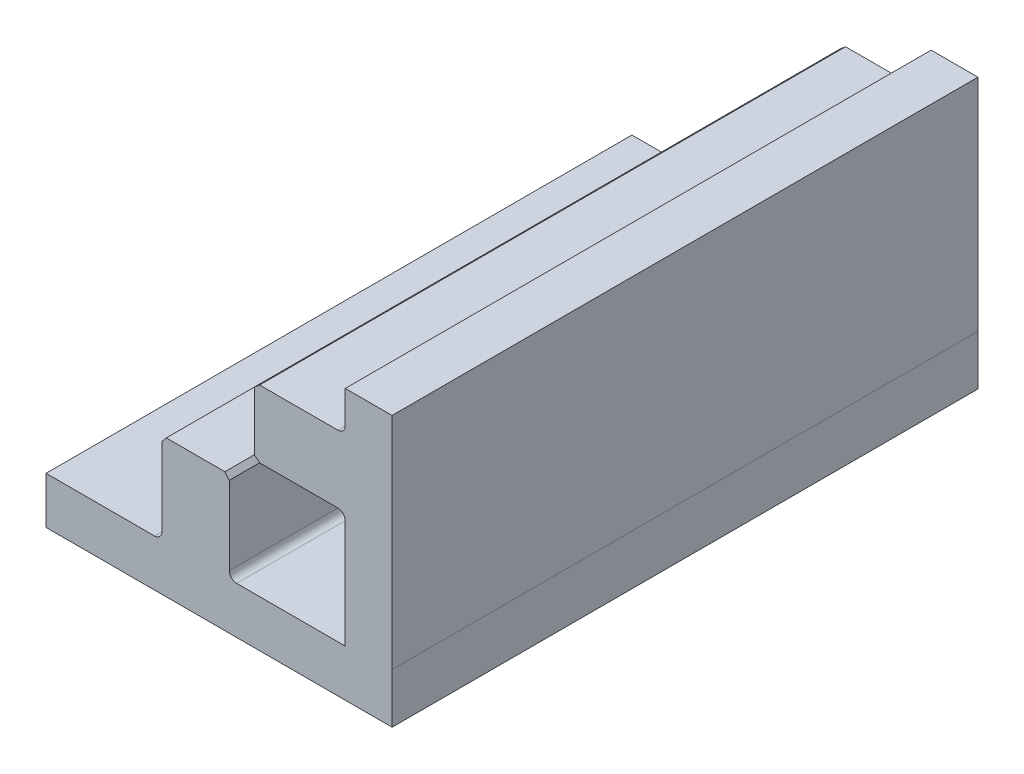
SolidWorks part; units mm, degrees
ref_plane "Front Plane" through (0, 0, 0) normal (0, 0, 1) x (1, 0, 0)
ref_plane "Top Plane" through (0, 0, 0) normal (0, 1, 0) x (1, 0, 0)
ref_plane "Right Plane" through (0, 0, 0) normal (1, 0, 0) x (0, 0, -1)
ref_plane "Plane1" through (0, 0, -3683) normal (0, 0, -1) x (-1, 0, 0)
sketch "Sketch1" plane through (0, 0, -3683) normal (0, 0, -1) x (-1, 0, 0)
  line L0 (7.9453, 3.5889) -> (-1.1987, 3.5889)
  line L1 (-1.8337, 4.2239) -> (-1.8337, 5.7479)
  line L2 (-1.1987, 6.3829) -> (1.6216, 6.3829)
  line L3 (1.6216, 6.3829) -> (1.6216, 6.8909)
  line L4 (1.6216, 6.8909) -> (-2.2147, 11.4629)
  line L5 (-2.2147, 11.4629) -> (-7.2947, 11.4629)
  line L6 (-7.2947, 11.4629) -> (-11.1311, 6.8909)
  line L7 (-11.1311, 6.8909) -> (-11.1311, 6.3829)
  line L8 (-11.1311, 6.3829) -> (-8.3107, 6.3829)
  line L9 (-7.6757, 5.7479) -> (-7.6757, 4.2239)
  line L10 (-8.3107, 3.5889) -> (-17.4547, 3.5889)
  line L11 (-17.7279, 3.8588) -> (-17.7284, 13.0024)
  line L12 (-17.4548, -0.4751) -> (7.9452, -0.4751)
  line L13 (-17.0929, 13.6378) -> (-15.5689, 13.6378)
  line L29 (-17.4547, 3.5889) -> (-17.7279, 3.5889)
  line L30 (-17.4548, -0.4751) -> (-17.7279, -0.4751)
  line L32 (8.2155, 3.5889) -> (8.2155, -0.4751)
  line L34 (8.2155, 3.5889) -> (7.9453, 3.5889)
  line L35 (8.2155, -0.4751) -> (7.9452, -0.4751)
  line L36 (-14.9339, 13.0028) -> (-14.9339, 10.1825)
  line L37 (-14.9339, 10.1825) -> (-14.4259, 10.1825)
  line L38 (-14.4259, 10.1825) -> (-9.8539, 14.0188)
  line L39 (-9.8539, 14.0188) -> (-9.8539, 19.0988)
  line L40 (-9.8539, 19.0988) -> (-14.4259, 22.9352)
  line L41 (-14.4259, 22.9352) -> (-14.9339, 22.9352)
  line L42 (-14.9339, 22.9352) -> (-14.9339, 20.1148)
  line L43 (-15.5689, 19.4798) -> (-17.0929, 19.4798)
  line L44 (-17.7287, 20.1156) -> (-17.7288, 22.9352)
  line L45 (-21.7872, 22.9352) -> (-21.7919, 3.8591)
  line L49 (-17.7288, 22.9352) -> (-21.7872, 22.9352)
  line L51 (-17.7279, 3.5889) -> (-17.7279, 3.8588)
  line L52 (-21.7919, 3.5889) -> (-21.7919, 3.8591)
  line L54 (-17.7279, -0.4751) -> (-21.7919, -0.4751)
  line L56 (-21.7919, -0.4751) -> (-21.7919, 3.5889)
  arc A0 (-1.1987, 3.5889) -> (-1.8337, 4.2239) centre (-1.1987, 4.2239) cw
  arc A1 (-1.8337, 5.7479) -> (-1.1987, 6.3829) centre (-1.1987, 5.7479) cw
  arc A2 (-8.3107, 6.3829) -> (-7.6757, 5.7479) centre (-8.3107, 5.7479) cw
  arc A3 (-7.6757, 4.2239) -> (-8.3107, 3.5889) centre (-8.3107, 4.2239) cw
  arc A4 (-17.7284, 13.0024) -> (-17.0929, 13.6378) centre (-17.0929, 13.0024) cw
  arc A5 (-15.5689, 13.6378) -> (-14.9339, 13.0028) centre (-15.5689, 13.0028) cw
  arc A6 (-14.9339, 20.1148) -> (-15.5689, 19.4798) centre (-15.5689, 20.1148) cw
  arc A7 (-17.0929, 19.4798) -> (-17.7287, 20.1156) centre (-17.0929, 20.1156) cw
extrude "Boss-Extrude1" add sketch "Sketch1" along normal blind 50.8
sketch "Sketch2" plane through (0, 0, -3683) normal (0, 0, 1) x (1, 0, 0)
  line L0 (11.1311, 6.8909) -> (11.1311, 6.3829) construction
  line L1 (11.1311, 6.3829) -> (8.3107, 6.3829) construction
  line L2 (7.2947, 11.4629) -> (11.1311, 6.8909) construction
  line L3 (4.7547, 11.4629) -> (4.7547, -3.7872) construction
  line L4 (7.6757, 5.7479) -> (7.6757, 4.2239) construction
  line L5 (11.1311, 6.8909) -> (11.1311, 6.3829)
  line L6 (11.1311, 6.3829) -> (8.3107, 6.3829)
  line L7 (7.6757, 11.0088) -> (11.1311, 6.8909)
  line L8 (2.2147, 11.4629) -> (7.2947, 11.4629) construction
  line L9 (7.6757, 5.7479) -> (7.6757, 11.0088)
  line L10 (1.8337, 5.7479) -> (1.8337, 11.0088)
  line L11 (1.8337, 11.0088) -> (-1.6216, 6.8909)
  line L12 (-1.6216, 6.3829) -> (1.1987, 6.3829)
  line L13 (-1.6216, 6.8909) -> (-1.6216, 6.3829)
  arc A0 (8.3107, 6.3829) -> (7.6757, 5.7479) centre (8.3107, 5.7479) ccw construction
  arc A1 (8.3107, 6.3829) -> (7.6757, 5.7479) centre (8.3107, 5.7479) ccw
  arc A2 (1.1987, 6.3829) -> (1.8337, 5.7479) centre (1.1987, 5.7479) cw
extrude "Cut-Extrude1" cut sketch "Sketch2" against normal up to next
sketch "Sketch3" plane through (0, 0, -3683) normal (0, 0, 1) x (1, 0, 0)
  line L0 (15.5689, 19.4798) -> (17.0929, 19.4798) construction
  line L1 (14.9339, 22.9352) -> (14.9339, 20.1148) construction
  line L2 (14.4259, 22.9352) -> (14.9339, 22.9352) construction
  line L3 (9.8539, 19.0988) -> (14.4259, 22.9352) construction
  line L4 (15.5689, 19.4798) -> (10.308, 19.4798)
  line L5 (14.9339, 22.9352) -> (14.9339, 20.1148)
  line L6 (14.4259, 22.9352) -> (14.9339, 22.9352)
  line L7 (10.308, 19.4798) -> (14.4259, 22.9352)
  line L8 (9.8539, 16.5588) -> (24.7491, 16.5588) construction
  line L9 (9.8539, 14.0188) -> (9.8539, 19.0988) construction
  line L10 (10.308, 13.6378) -> (14.4259, 10.1825)
  line L11 (14.4259, 10.1825) -> (14.9339, 10.1825)
  line L12 (14.9339, 10.1825) -> (14.9339, 13.0028)
  line L13 (15.5689, 13.6378) -> (10.308, 13.6378)
  arc A0 (14.9339, 20.1148) -> (15.5689, 19.4798) centre (15.5689, 20.1148) ccw construction
  arc A1 (14.9339, 20.1148) -> (15.5689, 19.4798) centre (15.5689, 20.1148) ccw
  arc A2 (14.9339, 13.0028) -> (15.5689, 13.6378) centre (15.5689, 13.0028) cw
extrude "Cut-Extrude2" cut sketch "Sketch3" against normal up to next
sketch "Sketch4" plane through (0, 0, -3683) normal (0, 0, 1) x (1, 0, 0)
  line L0 (2.2147, 11.4629) -> (7.2947, 11.4629) construction
  line L1 (9.8539, 14.0188) -> (9.8539, 19.0988) construction
  point P0 (4.7547, 11.4629)
  point P1 (9.8539, 16.5588)
